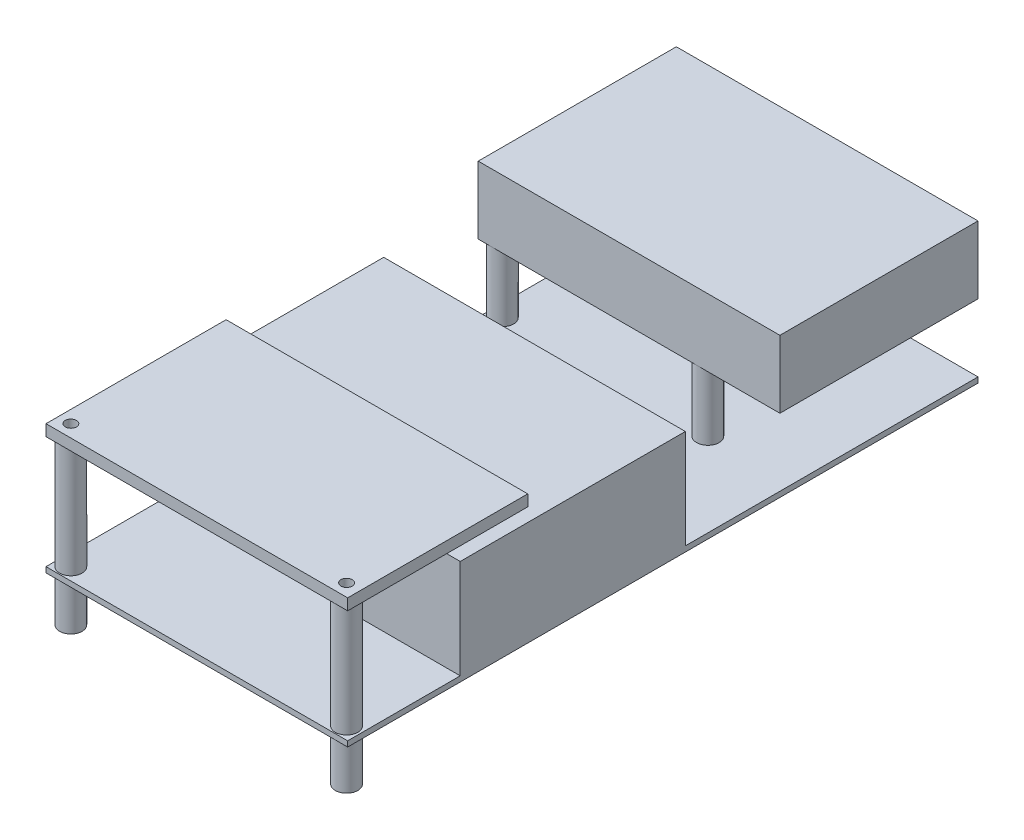
SolidWorks part; units mm, degrees
ref_plane "Front Plane" through (0, 0, 0) normal (0, 0, 1) x (1, 0, 0)
ref_plane "Top Plane" through (0, 0, 0) normal (0, 1, 0) x (1, 0, 0)
ref_plane "Right Plane" through (0, 0, 0) normal (1, 0, 0) x (0, 0, -1)
sketch "Sketch1" plane through (0, 0, 0) normal (0, 1, 0) x (1, 0, 0)
  line L1 (0, 0) -> (85.09, 0)
  line L2 (0, 0) -> (0, 177.8)
  line L3 (0, 177.8) -> (85.09, 177.8)
  line L4 (85.09, 0) -> (85.09, 177.8)
  dimension "D1" = 85.09
  dimension "D2" = 177.8
extrude "Boss-Extrude1" add sketch "Sketch1" along normal blind 1.524
sketch "Sketch2" plane through (0, 1.524, 0) normal (0, 1, 0) x (1, 0, 0)
  line L0 (0, 177.8) -> (0, 0) construction
  line L1 (0, 0) -> (85.09, 0) construction
  circle A0 centre (3.5052, 3.5052) radius 1.5875
  circle A1 centre (81.28, 3.5052) radius 1.5875
  circle A2 centre (3.5052, 174.244) radius 1.5875
  circle A3 centre (3.5052, 125.222) radius 1.5875
  circle A4 centre (61.468, 125.222) radius 1.5875
  circle A5 centre (61.468, 174.244) radius 1.5875
  dimension "D1" = 3.175
  dimension "D2" = 3.5052
  dimension "D3" = 3.5052
  dimension "D4" = 81.28
  dimension "D5" = 125.222
  dimension "D6" = 174.244
  dimension "D7" = 61.468
extrude "Cut-Extrude1" cut sketch "Sketch2" against normal through all
sketch "Sketch3" plane through (0, 1.524, 0) normal (0, 1, 0) x (1, 0, 0)
  line L0 (0, 177.8) -> (0, 0) construction
  line L1 (0, 31.75) -> (85.09, 31.75)
  line L2 (0, 31.75) -> (0, 95.25)
  line L3 (0, 95.25) -> (85.09, 95.25)
  line L4 (85.09, 31.75) -> (85.09, 95.25)
  line L5 (85.09, 0) -> (85.09, 177.8) construction
  line L6 (0, 0) -> (85.09, 0) construction
  dimension "D1" = 31.75
  dimension "D2" = 95.25
extrude "Boss-Extrude2" add sketch "Sketch3" along normal blind 27.94
sketch "Sketch4" plane through (0, 1.524, 0) normal (0, 1, 0) x (1, 0, 0)
  circle A0 centre (3.5052, 174.244) radius 3.175
  circle A1 centre (61.468, 174.244) radius 3.175
  circle A2 centre (3.5052, 125.222) radius 3.175
  circle A3 centre (61.468, 125.222) radius 3.175
  dimension "D1" = 6.35
extrude "Boss-Extrude3" add sketch "Sketch4" along normal blind 19.05
sketch "Sketch5" plane through (0, 20.574, 0) normal (0, 1, 0) x (1, 0, 0)
  line L1 (0, 121.92) -> (85.09, 121.92)
  line L2 (0, 121.92) -> (0, 177.8)
  line L3 (0, 177.8) -> (85.09, 177.8)
  line L4 (0, 95.25) -> (85.09, 95.25)
  line L5 (85.09, 95.25) -> (85.09, 177.8)
  line L6 (85.09, 177.8) -> (0, 177.8)
  line L7 (0, 177.8) -> (0, 95.25)
  line L8 (0, 95.25) -> (85.09, 95.25)
  line L9 (85.09, 95.25) -> (85.09, 177.8)
  line L10 (85.09, 177.8) -> (0, 177.8)
  line L11 (0, 177.8) -> (0, 95.25)
  line L12 (85.09, 121.92) -> (85.09, 177.8)
  circle A1 centre (3.5052, 174.244) radius 3.175
  circle A2 centre (3.5052, 174.244) radius 3.175
  circle M8 centre (3.5052, 174.244) radius 3.175
  dimension "D3" = 55.88
  dimension "D1" = 0
  dimension "D2" = 0
extrude "Boss-Extrude4" add sketch "Sketch5" along normal blind 19.05 contours L1 L9 L3 L2 M8 | M8 region at (42.8068, 20.574, -149.6965) region at (3.5052, 20.574, -174.244)
sketch "Sketch6" plane through (0, 0, 0) normal (0, -1, 0) x (1, 0, 0)
  circle A0 centre (3.5052, -3.5052) radius 3.175
  circle A1 centre (81.28, -3.5052) radius 3.175
  circle A2 centre (61.468, -125.222) radius 3.175
  circle A3 centre (3.5052, -125.222) radius 3.175
  circle A4 centre (3.5052, -174.244) radius 3.175
  circle A5 centre (61.468, -174.244) radius 3.175
  dimension "D1" = 6.35
extrude "Boss-Extrude5" add sketch "Sketch6" along normal blind 12.7
sketch "Sketch7" plane through (0, 1.524, 0) normal (0, 1, 0) x (1, 0, 0)
  circle A0 centre (3.5052, 3.5052) radius 3.175
  circle A1 centre (81.28, 3.5052) radius 3.175
  dimension "D1" = 6.35
extrude "Boss-Extrude6" add sketch "Sketch7" along normal blind 31.75 contours A0 | A1
sketch "Sketch8" plane through (0, 33.274, 0) normal (0, 1, 0) x (1, 0, 0)
  line L0 (85.09, 31.75) -> (85.09, 95.25) construction
  line L1 (0, 0) -> (85.09, 0)
  line L2 (0, 0) -> (0, 50.8)
  line L3 (0, 50.8) -> (85.09, 50.8)
  line L4 (85.09, 0) -> (85.09, 50.8)
  circle A0 centre (3.5052, 3.5052) radius 1.5875
  circle A1 centre (3.5052, 3.5052) radius 3.175
  circle A2 centre (3.5052, 3.5052) radius 3.175
  circle A3 centre (81.28, 3.5052) radius 1.5875
  circle M3 centre (3.5052, 3.5052) radius 3.175
  dimension "D3" = 3.175
  dimension "D2" = 50.8
  dimension "D1" = 0
extrude "Boss-Extrude7" add sketch "Sketch8" along normal blind 3.175 contours L1 L4 L3 L2 A3 M3 | A0 M3 region at (42.7621, 33.274, -25.6024) region at (0.42, 33.274, -3.5052)
